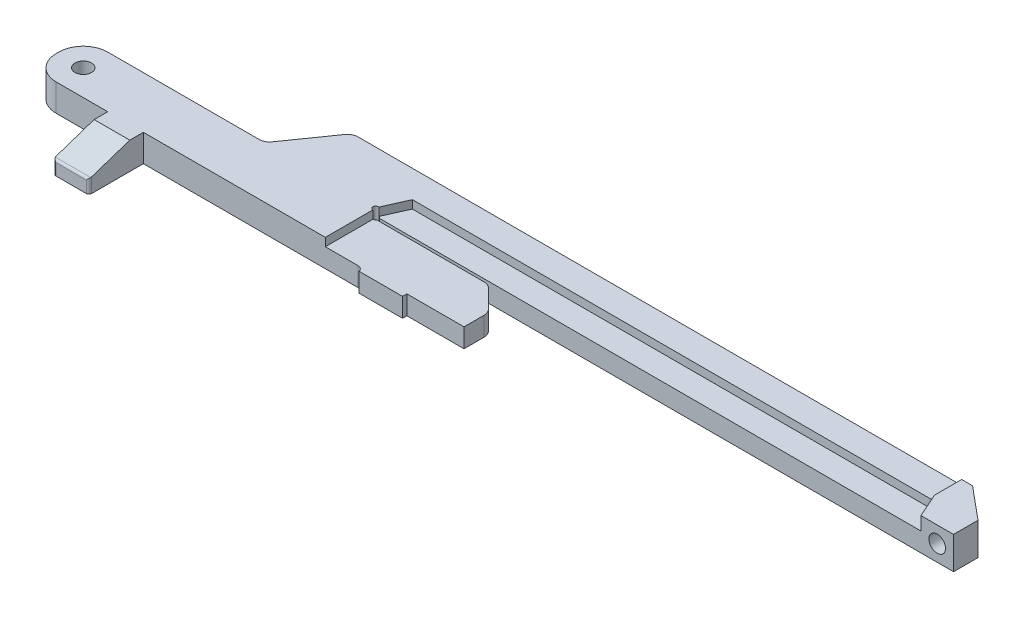
SolidWorks part; units mm, degrees
ref_plane "前视基准面" through (0, 0, 0) normal (0, 0, 1) x (1, 0, 0)
ref_plane "上视基准面" through (0, 0, 0) normal (0, 1, 0) x (1, 0, 0)
ref_plane "右视基准面" through (0, 0, 0) normal (1, 0, 0) x (0, 0, -1)
sketch "草图1" plane through (0, 0, 0) normal (0, 1, 0) x (1, 0, 0)
  line L0 (0, -4.75) -> (4.75, -4.75) construction
  line L1 (0, 0) -> (33.3333, 0)
  line L2 (0, 0) -> (0, -9.5)
  line L3 (0, -9.5) -> (14, -9.5)
  line L5 (0, -9.5) -> (14, -9.5)
  line L6 (20.55, -9.5) -> (20.55, -19.5)
  line L7 (20.55, -19.5) -> (14, -19.5)
  line L8 (14, -19.5) -> (14, -9.5)
  line L9 (20.55, -9.5) -> (61, -9.5)
  line L10 (0, -4.75) -> (54, -4.75) construction
  line L11 (54, -4.75) -> (54, 0) construction
  line L12 (54, 0) -> (54, 4.5) construction
  line L13 (54, 4.5) -> (54, 9.5) construction
  line L14 (54, 9.5) -> (44, 9.5)
  line L15 (44, 9.5) -> (40, 9.5)
  line L16 (34, -4.75) -> (44, 9.5) construction
  line L17 (54, -4.75) -> (34, -4.75) construction
  line L18 (40, 9.5) -> (33.3333, 0)
  line L19 (54, 9.5) -> (154, 9.5)
  line L20 (154, 9.5) -> (160, 9.5) construction
  line L21 (160, 9.5) -> (160, 4.5) construction
  line L22 (154, 9.5) -> (160, 4.5)
  line L23 (160, 4.5) -> (160, 0)
  line L24 (54, 0) -> (54, -0.5) construction
  line L25 (54.433, -0.5) -> (67, -0.5)
  line L26 (67, -0.5) -> (67, -9.5) construction
  line L27 (54.433, 0) -> (160, 0)
  line L28 (20.55, -19.5) -> (20.55, -20.6655)
  line L29 (67, -0.5) -> (70, -0.5)
  line L30 (70, -0.5) -> (70, -9.5) construction
  line L31 (69, -9.5) -> (70, -9.5)
  line L32 (69, -9.5) -> (69, -10.3)
  line L33 (69, -10.3) -> (61, -10.3)
  line L34 (61, -10.3) -> (61, -9.5)
  line L35 (70, -0.5) -> (79.5, -0.5)
  line L36 (79.5, -0.5) -> (79.5, -9.5)
  line L37 (79.5, -9.5) -> (70, -9.5)
  circle A0 centre (4.75, -4.75) radius 1.525
  arc A1 (54.433, 0) -> (54.433, -0.5) centre (54, -0.25) ccw
  dimension "D3" = 14
  dimension "D1" = 9.5
  dimension "D2" = 160
  dimension "D4" = 6.55
  dimension "D5" = 10
  dimension "D6" = 4.5
  dimension "D7" = 5
  dimension "D8" = 10
  dimension "D9" = 4
  dimension "D10" = 54
  dimension "D11" = 100
extrude "凸台-拉伸2" add sketch "草图1" along normal blind 5 contours L6 L9 L1 L2 A0 L3 L8 L7 region at (73.0841, 0, -0.4255)
sketch "草图2" plane through (0, 0, 0) normal (0, 1, 0) x (1, 0, 0)
  line L0 (67, -9.5) -> (54, -9.5) construction
  line L1 (54, -9.5) -> (54, -0.5)
  line L2 (54, -0.5) -> (67, -0.5)
  line L3 (67, -9.5) -> (67, -0.5) construction
  line L4 (54, 0) -> (154, 0)
  line L5 (54, 0) -> (54, 4.5) construction
  line L6 (54, 4.5) -> (56, 4.5) construction
  line L7 (56, 4.5) -> (54, 0)
  line L8 (56, 4.5) -> (152, 4.5)
  line L9 (152, 4.5) -> (154, 4.5) construction
  line L10 (154, 4.5) -> (154, 0) construction
  line L11 (154, 0) -> (152, 4.5)
  line L12 (54, -9.5) -> (54, -15.9553)
  line L13 (54, -15.9553) -> (83.5957, -15.9553)
  line L14 (83.5957, -15.9553) -> (83.5957, -0.5)
  line L15 (83.5957, -0.5) -> (67, -0.5)
extrude "切除-拉伸1" cut sketch "草图2" along normal through all from offset 3.5
sketch "草图3" plane through (0, 5, 0) normal (0, 1, 0) x (1, 0, 0)
  line L0 (152, 4.5) -> (152, 9.5)
  line L1 (40, 9.5) -> (154, 9.5) construction
  line L2 (152, 9.5) -> (154, 9.5)
  line L16 (20.55, -9.5) -> (54, -9.5)
  line L17 (54, -9.5) -> (54, -0.75)
  line L18 (54.1061, 0.2386) -> (56, 4.5)
  line L19 (56, 4.5) -> (152, 4.5)
  line L20 (152, 4.5) -> (154, 0)
  line L21 (154, 0) -> (160, 0)
  line L22 (160, 0) -> (160, 4.5)
  line L23 (160, 4.5) -> (154, 9.5)
  line L24 (154, 9.5) -> (40, 9.5)
  line L25 (40, 9.5) -> (33.3333, 0)
  line L26 (33.3333, 0) -> (0, 0)
  line L27 (0, 0) -> (0, -9.5)
  line L28 (0, -9.5) -> (14, -9.5)
  line L29 (14, -9.5) -> (14, -19.5)
  line L30 (14, -19.5) -> (20.55, -19.5)
  line L31 (20.55, -19.5) -> (20.55, -9.5)
  line L36 (152, 4.5) -> (154, 0)
  line L37 (154, 0) -> (160, 0)
  line L38 (160, 0) -> (160, 4.5)
  line L39 (160, 4.5) -> (154, 9.5)
  arc A1 (54.1061, 0.2386) -> (54, -0.75) centre (54, -0.25) ccw
  dimension "D1" = 0
extrude "凸台-拉伸4" add sketch "草图3" along normal blind 5.95 from offset 5 offset against normal yes
sketch "草图4" plane through (0, 0, 0) normal (0, 0, 1) x (1, 0, 0)
  line L0 (157, 5.95) -> (157, 2.975) construction
  line L6 (154, 5.95) -> (154, 3.5)
  line L7 (154, 3.5) -> (54.433, 3.5)
  line L8 (54.433, 3.5) -> (54.433, 0)
  line L9 (54.433, 0) -> (160, 0)
  line L10 (160, 0) -> (160, 5.95)
  line L11 (160, 5.95) -> (154, 5.95)
  line L12 (154, 5.95) -> (154, 3.5) construction
  line L16 (160, 0) -> (160, 5.95) construction
  line L17 (160, 5.95) -> (154, 5.95) construction
  circle A0 centre (157, 2.975) radius 1.525
  dimension "D1" = 0
extrude "切除-拉伸2" cut sketch "草图4" against normal through all
sketch "草图5" plane through (0, 0, 0) normal (0, 1, 0) x (1, 0, 0)
  circle A0 centre (4.75, -4.75) radius 1.525 construction
  circle A1 centre (4.75, -4.75) radius 1.525 construction
  circle A2 centre (4.75, -4.75) radius 3
extrude "切除-拉伸3" cut sketch "草图5" along normal blind 2
fillet "圆角1" radius 4.5 2 edges at (0, 2.5, 0) (0, 2.5, 9.5)
sketch "草图7" plane through (0, 0, 0) normal (1, 0, 0) x (0, 0, -1)
  line L1 (-12.5, 5) -> (-19.5, 2.5) construction
  line L2 (-19.5, 2.5) -> (-12, 5)
  line L3 (-19.5, 5) -> (-12, 5)
  line L4 (-19.5, 0) -> (-9.5, 0)
  line L5 (-19.5, 5) -> (-19.5, 0)
  line L6 (-9.5, 5) -> (-19.5, 5)
  line L7 (-9.5, 0) -> (-9.5, 5)
  line L9 (-19.5, 5) -> (-19.5, 2.5)
  dimension "D1" = 0
extrude "切除-拉伸4" cut sketch "草图7" along normal through all
fillet "圆角4" radius 0.5 3 edges at (20.55, 1.25, 19.5) (14, 1.25, 19.5) (17.275, 2.5, 19.5)
fillet "圆角5" radius 2 2 edges at (40, 2.5, -9.5) (33.3333, 2.5, 0)
fillet "圆角11" radius 1 1 edges at (61, 1.75, 9.5)
sketch "草图9" plane through (0, 0, 0) normal (0, 1, 0) x (1, 0, 0)
  line L1 (75, -0.5) -> (79.5, -5)
  line L7 (54, -0.75) -> (54, -9.5)
  line L8 (54, -9.5) -> (60.0202, -9.5)
  line L9 (61, -10.3) -> (69, -10.3)
  line L10 (69, -10.3) -> (69, -9.5)
  line L11 (69, -9.5) -> (79.5, -9.5)
  line L12 (79.5, -9.5) -> (79.5, -0.5)
  line L13 (79.5, -0.5) -> (54.433, -0.5)
  line L19 (79.5, -5) -> (79.5, -0.5)
  line L20 (79.5, -0.5) -> (75, -0.5)
  arc A2 (61, -10.3) -> (60.0202, -9.5) centre (60.0202, -10.5) ccw
  arc A3 (54, -0.75) -> (54.433, -0.5) centre (54, -0.25) ccw
  dimension "D1" = 0
extrude "切除-拉伸5" cut sketch "草图9" along normal blind 10
fillet "圆角12" radius 2 2 edges at (79.5, 1.75, 5) (75, 1.75, 0.5)
